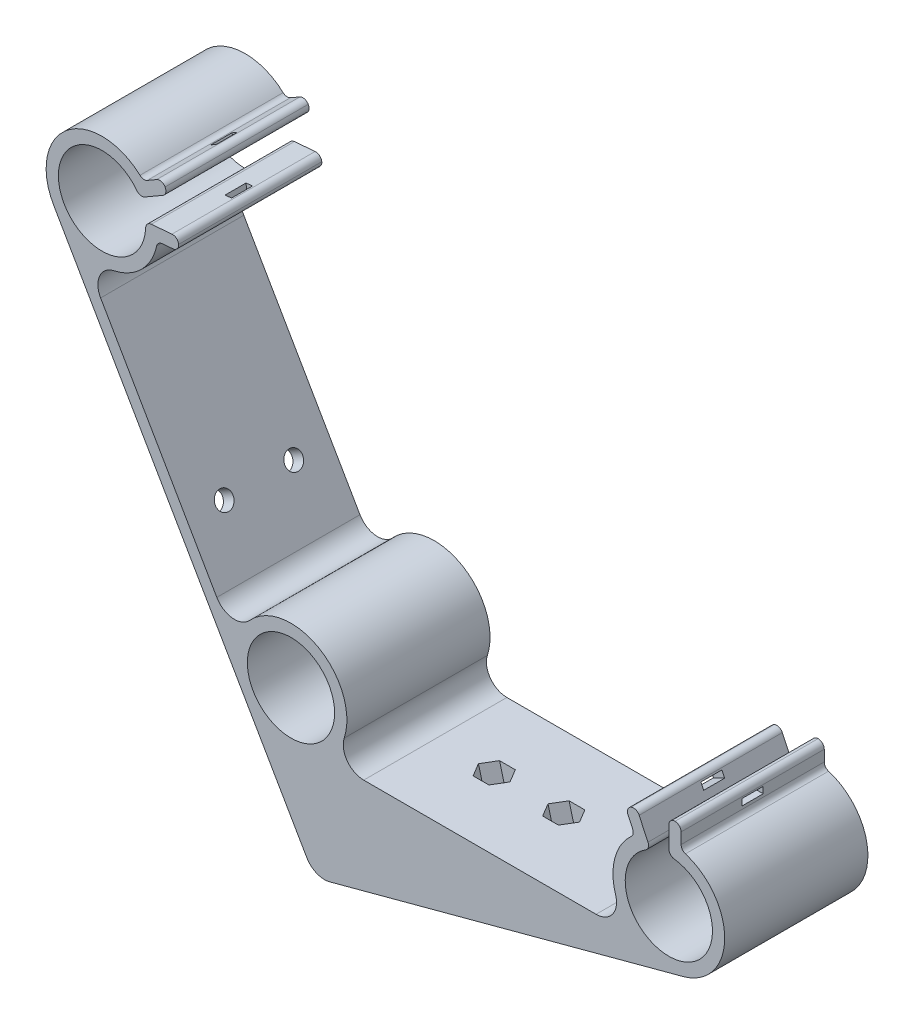
SolidWorks part; units mm, degrees
ref_plane "Front Plane" through (0, 0, 0) normal (0, 0, 1) x (1, 0, 0)
ref_plane "Top Plane" through (0, 0, 0) normal (0, 1, 0) x (1, 0, 0)
ref_plane "Right Plane" through (0, 0, 0) normal (1, 0, 0) x (0, 0, -1)
sketch "Sketch3" plane through (0, 0, 0) normal (0, 1, 0) x (1, 0, 0)
  line L1 (-57.15, -9.525) -> (57.15, -9.525)
  line L2 (-57.15, -9.525) -> (-57.15, 9.525)
  line L3 (-57.15, 9.525) -> (57.15, 9.525)
  line L4 (57.15, -9.525) -> (57.15, 9.525)
  line L5 (-57.15, -9.525) -> (57.15, 9.525) construction
  line L6 (-57.15, 9.525) -> (57.15, -9.525) construction
  point P0 (0, 0)
  dimension "D1" = 19.05
  dimension "D2" = 114.3
extrude "Boss-Extrude1" add sketch "Sketch3" along normal blind 3.81
sketch "Sketch4" plane through (0, 0, 0) normal (0, 0, 1) x (1, 0, 0)
  line L0 (-58.6588, 17.3553) -> (58.6588, 17.3553) construction
  line L1 (57.15, 3.81) -> (-57.15, 3.81) construction
  line L2 (0, -20.955) -> (0, 20.955) construction
  line L5 (-117.3176, 118.9553) -> (-102.2874, 127.633) construction
  line L8 (-57.15, 3.81) -> (57.15, 3.81) construction
  line L9 (-36.0719, 3.81) -> (36.0719, 3.81)
  line L11 (-57.15, 0) -> (57.15, 0) construction
  line L13 (0, 3.81) -> (0, 0)
  line L14 (58.6588, 0) -> (-58.6588, 0)
  line L15 (-58.6588, 17.3553) -> (-24.1786, 77.0768) construction
  line L16 (58.6588, 17.3553) -> (41.5671, 14.3416) construction
  line L17 (58.6588, 17.3553) -> (58.6588, 34.7106) construction
  line L18 (58.6588, 17.3553) -> (64.5947, 33.664) construction
  line L19 (41.5671, 14.3416) -> (45.3193, 15.0032)
  line L20 (58.6588, 34.7106) -> (58.6588, 30.9006)
  line L21 (-132.3477, 110.2777) -> (-73.6889, 8.6777)
  line L22 (-81.6828, 30.1435) -> (-117.7547, 92.6218)
  line L24 (-102.2874, 127.633) -> (-105.587, 125.728)
  line L25 (63.1507, 0.5914) -> (-46.6063, -28.8179)
  line L26 (-117.3176, 118.9553) -> (-100.0283, 120.4679) construction
  line L27 (-73.6889, 8.6777) -> (-53.749, -25.8593)
  line L28 (-73.6889, 8.6777) -> (-46.8802, -37.7565) construction
  line L29 (-100.0283, 120.4679) -> (-103.8238, 120.1359)
  line L30 (-102.2874, 127.633) -> (-96.7882, 130.808)
  line L31 (-96.7882, 130.808) -> (-98.6932, 134.1075)
  line L32 (-98.6932, 134.1075) -> (-104.5591, 130.7208)
  line L33 (-100.0283, 120.4679) -> (-93.7025, 121.0214)
  line L34 (-93.7025, 121.0214) -> (-93.3704, 117.2259)
  line L35 (-93.3704, 117.2259) -> (-100.118, 116.6355)
  line L36 (58.6588, 34.7106) -> (58.6588, 30.9006)
  line L37 (51.3241, 33.0846) -> (52.9343, 29.6315)
  line L38 (45.1875, 37.2294) -> (48.05, 31.0907)
  line L39 (48.6405, 38.8396) -> (45.1875, 37.2294)
  line L40 (51.3241, 33.0846) -> (48.6405, 38.8396)
  line L41 (58.6588, 34.7106) -> (58.6588, 41.0606)
  line L42 (58.6588, 41.0606) -> (62.4688, 41.0606)
  line L43 (62.4688, 41.0606) -> (62.4688, 34.2873)
  circle A0 centre (-58.6588, 17.3553) radius 13.5453
  arc A1 (45.3193, 15.0032) -> (63.2916, 30.0837) centre (58.6588, 17.3553) ccw
  arc A2 (-42.1223, 12.0874) -> (-76.0141, 17.3553) centre (-58.6588, 17.3553) ccw
  arc A3 (42.1223, 12.0874) -> (41.5671, 14.3416) centre (58.6588, 17.3553) cw
  arc A4 (-36.0719, 3.81) -> (-42.1223, 12.0874) centre (-36.0719, 10.16) cw
  arc A5 (36.0719, 3.81) -> (42.1223, 12.0874) centre (36.0719, 10.16) ccw
  arc A6 (42.1223, 12.0874) -> (41.5671, 14.3416) centre (58.6588, 17.3553) cw
  arc A7 (-42.1223, 12.0874) -> (-76.0141, 17.3553) centre (-58.6588, 17.3553) ccw
  arc A8 (41.5671, 14.3416) -> (42.1223, 12.0874) centre (58.6588, 17.3553) ccw
  arc A9 (64.5947, 33.664) -> (76.0141, 17.3553) centre (58.6588, 17.3553) cw
  arc A10 (64.5947, 33.664) -> (76.0141, 17.3553) centre (58.6588, 17.3553) cw
  arc A11 (58.6588, 0) -> (64.5947, 33.664) centre (58.6588, 17.3553) ccw
  arc A12 (63.2916, 30.0837) -> (58.6588, 30.9006) centre (58.6588, 17.3553) ccw
  arc A13 (64.5947, 33.664) -> (58.6588, 34.7106) centre (58.6588, 17.3553) ccw
  arc A15 (-76.0141, 17.3553) -> (-58.6588, 0) centre (-58.6588, 17.3553) ccw
  arc A16 (-132.3477, 110.2777) -> (-106.1618, 132.2503) centre (-117.3176, 118.9553) cw
  arc A17 (-113.6114, 102.0003) -> (-111.3817, 102.6467) centre (-117.3176, 118.9553) ccw
  arc A18 (-106.1618, 132.2503) -> (-102.2874, 127.633) centre (-117.3176, 118.9553) cw
  arc A19 (-108.6108, 129.3316) -> (-105.587, 125.728) centre (-117.3176, 118.9553) cw
  arc A20 (-106.1618, 132.2503) -> (-125.9952, 133.9855) centre (-117.3176, 118.9553) ccw
  arc A21 (-112.6848, 106.2269) -> (-108.6108, 129.3316) centre (-117.3176, 118.9553) cw
  arc A22 (-117.7547, 92.6218) -> (-113.6114, 102.0003) centre (-112.2554, 95.7968) cw
  arc A23 (-49.9811, 2.3252) -> (-73.6889, 8.6777) centre (-58.6588, 17.3553) cw
  arc A24 (-81.6828, 30.1435) -> (-71.4892, 29.0424) centre (-76.1836, 33.3185) ccw
  arc A25 (-71.4892, 29.0424) -> (-49.9811, 2.3252) centre (-58.6588, 17.3553) cw
  arc A26 (-46.6063, -28.8179) -> (-53.749, -25.8593) centre (-48.2498, -22.6843) cw
  arc A27 (-105.587, 125.728) -> (-103.8238, 120.1359) centre (-117.3176, 118.9553) ccw
  arc A28 (-102.2874, 127.633) -> (-100.0283, 120.4679) centre (-117.3176, 118.9553) ccw
  arc A29 (58.6588, 30.9006) -> (52.9343, 29.6315) centre (58.6588, 17.3553) cw
  arc A30 (63.2916, 30.0837) -> (58.6588, 30.9006) centre (58.6588, 17.3553) ccw
  arc A31 (58.6588, 34.7106) -> (51.3241, 33.0846) centre (58.6588, 17.3553) cw
  point P6 (0, 17.3553)
  point P28 (-47.8084, 3.81)
  dimension "D1" = 27.0906
  dimension "D4" = 3.81
  dimension "D5" = 6.35
  dimension "D9" = 6.35
  dimension "D2" = 117.3176
  dimension "D3" = 60
  dimension "D6" = 100
  dimension "D7" = 20
  dimension "D8" = 15
  dimension "D10" = 25
  dimension "D11" = 3.81
  dimension "D12" = 6.35
  dimension "D13" = 3.81
  dimension "D14" = 6.35
sketch "Sketch5" plane through (0, 3.81, 0) normal (0, 1, 0) x (1, 0, 0)
  line L0 (0, -14.8995) -> (0, 14.8995) construction
  line L1 (57.15, 9.525) -> (-57.15, 9.525) construction
  line L2 (0, 13.545) -> (0, 9.525) construction
  line L3 (-95.7369, 0) -> (95.7369, 0) construction
  line L4 (0, -13.545) -> (0, -9.525) construction
  line L5 (-17.78, 9.525) -> (-17.78, -9.525) construction
  line L6 (-57.15, -9.525) -> (57.15, -9.525) construction
  circle A0 centre (0, 10.795) radius 2.75 construction
  circle A1 centre (0, -10.795) radius 2.75 construction
  circle A2 centre (-17.78, 10.795) radius 2.75 construction
  circle A3 centre (-17.78, -10.795) radius 2.75 construction
  circle A4 centre (-17.78, 0) radius 2.75
  circle A5 centre (3.81, 0) radius 2.75
  dimension "D2" = 5.5
  dimension "D1" = 21.59
  dimension "D4" = 21.59
  dimension "D3" = 17.78
extrude "Boss-Extrude2" add sketch "Sketch4" along normal mid plane 44.45 contours A0 A2 L13 L9 A4 | A5 L9 L13 A6 A1 A3 | A25 A2 A7 A15 A23 A0 | A24 L22 A22 A17 A21 A19 L24 A18 A16 L21 A15 A7 | A26 L14 A15 L27 | A28 L21 A15 A7 A24 L22 A22 | L32 A18 L30 L31 | A28 L35 L34 L33 | A31 A11 A9 A13 L20 A12 A1 L19 A3 | A31 L19 A29 L37 | L38 A31 L40 L39 | A13 L43 L42 L41 region at (-27.6447, 2.2944, 0) region at (27.6447, 2.2944, 0) region at (-45.5221, 6.78, 0) region at (-19.9969, -9.8836, 0) region at (-101.0313, 60.6249, 0) region at (42.2818, 13.3222, 0) region at (45.8473, 24.0246, 0) region at (48.2673, 35.0835, 0) region at (-133.6074, 123.3201, 0) region at (60.5844, 37.8142, 0) region at (-96.7687, 118.8201, 0) region at (-100.5625, 130.8524, 0)
extrude "Cut-Extrude4" [suppressed] cut sketch "Sketch5" against normal blind 12.7
sketch "Sketch6" plane through (-48.2096, -27.8338, 0) normal (0.866, 0.5, 0) x (0, 0, -1)
  line L0 (-22.225, 103.0183) -> (22.225, 103.0183) construction
  line L1 (-22.225, 66.9465) -> (-22.225, 139.0902) construction
  line L2 (22.225, 66.9465) -> (22.225, 139.0902) construction
  line L3 (-22.225, 85.2383) -> (22.225, 85.2383) construction
  line L4 (0, 95.7369) -> (0, -95.7369) construction
  circle A0 centre (-10.795, 85.2383) radius 2.75
  circle A1 centre (10.795, 85.2383) radius 2.75
  dimension "D1" = 5.5
  dimension "D2" = 21.59
  dimension "D3" = 17.78
extrude "Cut-Extrude5" cut sketch "Sketch6" against normal blind 7.62
sketch "Sketch7" plane through (4.0825, -15.2359, 0) normal (0.2588, -0.9659, 0) x (0.9659, 0.2588, 0)
  ellipse E0 centre (4.6663, 0) end of major axis (4.6663, -2.75) minor radius 2.6563 construction
  ellipse E1 centre (-16.1881, 0) end of major axis (-16.1881, -2.75) minor radius 2.6563 construction
  ellipse E2 centre (4.6663, 0) end of major axis (4.6663, -2.75) minor radius 2.6563
  ellipse E3 centre (-16.1881, 0) end of major axis (-16.1881, -2.75) minor radius 2.6563
extrude "Cut-Extrude7" cut sketch "Sketch7" against normal up to next
sketch "Sketch11" plane through (4.0825, -15.2359, 0) normal (0.2588, -0.9659, 0) x (0.9659, 0.2588, 0)
  line L0 (95.7369, 0) -> (-95.7369, 0) construction
  line L1 (-11.4538, 0) -> (-13.8209, 4.1)
  line L2 (-13.8209, 4.1) -> (-18.5552, 4.1)
  line L3 (-18.5552, 4.1) -> (-20.9223, 0)
  line L4 (-20.9223, 0) -> (-18.5552, -4.1)
  line L5 (-18.5552, -4.1) -> (-13.8209, -4.1)
  line L6 (-13.8209, -4.1) -> (-11.4538, 0)
  line L7 (9.4006, 0) -> (7.0334, 4.1)
  line L8 (7.0334, 4.1) -> (2.2991, 4.1)
  line L9 (2.2991, 4.1) -> (-0.068, 0)
  line L10 (-0.068, 0) -> (2.2991, -4.1)
  line L11 (2.2991, -4.1) -> (7.0334, -4.1)
  line L12 (7.0334, -4.1) -> (9.4006, 0)
  circle A0 centre (-16.1881, 0) radius 4.1 construction
  circle A1 centre (4.6663, 0) radius 4.1 construction
  dimension "D1" = 8.2
  dimension "D2" = 60
  dimension "D3" = 60
extrude "Cut-Extrude8" cut sketch "Sketch11" against normal up to next from offset 12.7 offset against normal yes
sketch "Sketch14" plane through (-82.7436, 143.316, 0) normal (-0.5, 0.866, 0) x (0.866, 0.5, 0)
  line L0 (-25.1904, 0) -> (-18.417, 0) construction
  line L1 (-25.1904, -22.225) -> (-25.1904, 22.225) construction
  line L2 (-18.417, -22.225) -> (-18.417, 22.225) construction
  line L4 (-22.8037, -3.25) -> (-20.8037, -3.25)
  line L5 (-22.8037, -3.25) -> (-22.8037, 3.25)
  line L6 (-22.8037, 3.25) -> (-20.8037, 3.25)
  line L7 (-20.8037, -3.25) -> (-20.8037, 3.25)
  line L8 (-22.8037, -3.25) -> (-20.8037, 3.25) construction
  line L9 (-22.8037, 3.25) -> (-20.8037, -3.25) construction
  point P6 (-21.8037, 0)
  dimension "D1" = 6.5
  dimension "D2" = 2
extrude "Cut-Extrude9" cut sketch "Sketch14" against normal up to next
ref_plane "Plane1" through (-44.7233, 141.8442, 0) normal (0.3007, -0.9537, 0) x (-0.9537, -0.3007, 0)
mirror "Mirror1" about plane through (-44.7233, 141.8442, 0) normal (0.3007, -0.9537, 0) of "Cut-Extrude9"
ref_plane "Plane2" through (-51.5092, 29.7388, 0) normal (0.866, -0.5, 0) x (0.5, 0.866, 0)
mirror "Mirror2" about plane through (-51.5092, 29.7388, 0) normal (0.866, -0.5, 0) of "Mirror1", "Cut-Extrude9"
fillet "Fillet1" radius 1.905 16 edges at (-105.587, 125.728, 0) (-103.8238, 120.1359, 0) (-100.118, 116.6355, 0) (-104.5591, 130.7208, 0) (52.9343, 29.6315, 0) (58.6588, 30.9006, 0) (48.05, 31.0907, 0) (62.4688, 34.2873, 0) (62.4688, 41.0606, 0) (45.1875, 37.2294, 0) (48.6405, 38.8396, 0) (58.6588, 41.0606, 0) (-93.3704, 117.2259, 0) (-93.7025, 121.0214, 0) (-96.7882, 130.808, 0) (-98.6932, 134.1075, 0)
sketch "Sketch15" [suppressed] plane through (0, 0, 9.525) normal (0, 0, 1) x (1, 0, 0)
  line L4 (-104.0393, 126.6215) -> (-98.438, 129.8555)
  line L8 (-100.343, 133.155) -> (-103.2939, 131.4513)
  line L11 (-132.3477, 110.2777) -> (-53.749, -25.8593)
  line L20 (36.0719, 3.81) -> (-36.0719, 3.81)
  line L23 (-132.3477, 110.2777) -> (-53.749, -25.8593)
  line L32 (36.0719, 3.81) -> (-36.0719, 3.81)
  line L36 (-46.6063, -28.8179) -> (63.1507, 0.5914)
  line L37 (-46.6063, -28.8179) -> (63.1507, 0.5914)
  line L38 (62.4688, 35.7482) -> (62.4688, 39.1556)
  line L39 (62.4688, 35.7482) -> (62.4688, 39.1556)
  line L40 (58.6588, 39.1556) -> (58.6588, 32.6877)
  line L41 (58.6588, 39.1556) -> (58.6588, 32.6877)
  line L42 (52.179, 31.2512) -> (49.4456, 37.1131)
  line L43 (52.179, 31.2512) -> (49.4456, 37.1131)
  line L44 (45.9925, 35.5029) -> (47.4326, 32.4148)
  line L45 (45.9925, 35.5029) -> (47.4326, 32.4148)
  line L46 (-81.6828, 30.1435) -> (-117.7547, 92.6218)
  line L47 (-98.6626, 116.7629) -> (-95.2682, 117.0598)
  line L48 (-95.6002, 120.8553) -> (-102.0435, 120.2916)
  arc A0 (-49.9811, 2.3252) -> (-71.4892, 29.0424) centre (-58.6588, 17.3553) ccw construction
  arc A1 (-73.6889, 8.6777) -> (-49.9811, 2.3252) centre (-58.6588, 17.3553) ccw construction
  arc A2 (-76.0141, 17.3553) -> (-58.6588, 0) centre (-58.6588, 17.3553) ccw construction
  arc A3 (-49.9811, 2.3252) -> (-42.1223, 12.0874) centre (-58.6588, 17.3553) ccw
  arc A4 (-73.6889, 8.6777) -> (-49.9811, 2.3252) centre (-58.6588, 17.3553) ccw
  arc A5 (-73.6889, 8.6777) -> (-58.6588, 0) centre (-58.6588, 17.3553) ccw
  arc A39 (-106.5116, 127.1227) -> (-103.7812, 118.4631) centre (-117.3176, 118.9553) ccw
  arc A40 (-106.5116, 127.1227) -> (-104.0393, 126.6215) centre (-104.9918, 128.2713) ccw
  arc A41 (-98.438, 129.8555) -> (-97.7407, 132.4577) centre (-99.3905, 131.5052) ccw
  arc A42 (-97.7407, 132.4577) -> (-100.343, 133.155) centre (-99.3905, 131.5052) ccw
  arc A43 (-105.5392, 131.702) -> (-103.2939, 131.4513) centre (-104.2464, 133.1011) ccw
  arc A44 (-105.5392, 131.702) -> (-132.3477, 110.2777) centre (-117.3176, 118.9553) ccw
  arc A45 (-53.749, -25.8593) -> (-46.6063, -28.8179) centre (-48.2498, -22.6843) ccw
  arc A46 (-53.749, -25.8593) -> (-46.6063, -28.8179) centre (-48.2498, -22.6843) ccw
  arc A47 (63.1507, 0.5914) -> (63.8085, 33.929) centre (58.6588, 17.3553) ccw
  arc A48 (63.1507, 0.5914) -> (63.8085, 33.929) centre (58.6588, 17.3553) ccw
  arc A51 (62.4688, 35.7482) -> (63.8085, 33.929) centre (64.3738, 35.7482) ccw
  arc A84 (62.4688, 35.7482) -> (63.8085, 33.929) centre (64.3738, 35.7482) ccw
  arc A85 (62.4688, 39.1556) -> (60.5638, 41.0606) centre (60.5638, 39.1556) ccw
  arc A86 (62.4688, 39.1556) -> (60.5638, 41.0606) centre (60.5638, 39.1556) ccw
  arc A87 (60.5638, 41.0606) -> (58.6588, 39.1556) centre (60.5638, 39.1556) ccw
  arc A88 (60.5638, 41.0606) -> (58.6588, 39.1556) centre (60.5638, 39.1556) ccw
  arc A89 (58.6588, 32.6877) -> (60.3289, 30.7973) centre (60.5638, 32.6877) ccw
  arc A90 (58.6588, 32.6877) -> (60.3289, 30.7973) centre (60.5638, 32.6877) ccw
  arc A91 (51.4643, 28.832) -> (60.3289, 30.7973) centre (58.6588, 17.3553) ccw
  arc A92 (51.4643, 28.832) -> (60.3289, 30.7973) centre (58.6588, 17.3553) ccw
  arc A93 (51.4643, 28.832) -> (52.179, 31.2512) centre (50.4525, 30.4461) ccw
  arc A94 (51.4643, 28.832) -> (52.179, 31.2512) centre (50.4525, 30.4461) ccw
  arc A95 (49.4456, 37.1131) -> (46.914, 38.0345) centre (47.7191, 36.308) ccw
  arc A96 (49.4456, 37.1131) -> (46.914, 38.0345) centre (47.7191, 36.308) ccw
  arc A97 (46.914, 38.0345) -> (45.9925, 35.5029) centre (47.7191, 36.308) ccw
  arc A98 (46.914, 38.0345) -> (45.9925, 35.5029) centre (47.7191, 36.308) ccw
  arc A99 (46.9872, 30.1998) -> (47.4326, 32.4148) centre (45.7061, 31.6097) ccw
  arc A100 (46.9872, 30.1998) -> (47.4326, 32.4148) centre (45.7061, 31.6097) ccw
  arc A101 (46.9872, 30.1998) -> (42.1223, 12.0874) centre (58.6588, 17.3553) ccw
  arc A102 (46.9872, 30.1998) -> (42.1223, 12.0874) centre (58.6588, 17.3553) ccw
  arc A103 (36.0719, 3.81) -> (42.1223, 12.0874) centre (36.0719, 10.16) ccw
  arc A104 (36.0719, 3.81) -> (42.1223, 12.0874) centre (36.0719, 10.16) ccw
  arc A105 (-42.1223, 12.0874) -> (-36.0719, 3.81) centre (-36.0719, 10.16) ccw
  arc A106 (-42.1223, 12.0874) -> (-36.0719, 3.81) centre (-36.0719, 10.16) ccw
  arc A107 (-42.1223, 12.0874) -> (-71.4892, 29.0424) centre (-58.6588, 17.3553) ccw
  arc A108 (-81.6828, 30.1435) -> (-71.4892, 29.0424) centre (-76.1836, 33.3185) ccw
  arc A109 (-113.6114, 102.0003) -> (-117.7547, 92.6218) centre (-112.2554, 95.7968) ccw
  arc A110 (-113.6114, 102.0003) -> (-100.3581, 115.2697) centre (-117.3176, 118.9553) ccw
  arc A111 (-98.6626, 116.7629) -> (-100.3581, 115.2697) centre (-98.4966, 114.8651) ccw
  arc A112 (-95.2682, 117.0598) -> (-93.5364, 119.1236) centre (-95.4342, 118.9576) ccw
  arc A113 (-93.5364, 119.1236) -> (-95.6002, 120.8553) centre (-95.4342, 118.9576) ccw
  arc A114 (-102.0435, 120.2916) -> (-103.7812, 118.4631) centre (-101.8775, 118.3939) ccw
  dimension "D1" = 0
extrude "Cut-Extrude10" [suppressed] cut sketch "Sketch15" against normal through all both and the other way through all
sketch "Sketch16" [suppressed] plane through (-48.2096, -27.8338, 0) normal (0.866, 0.5, 0) x (0, 0, -1)
  line L0 (-9.525, 103.0183) -> (9.525, 103.0183) construction
  line L1 (-9.525, 66.9465) -> (-9.525, 139.0902) construction
  line L2 (9.525, 66.9465) -> (9.525, 139.0902) construction
  line L3 (0, 66.9465) -> (0, 139.0902) construction
  circle A0 centre (0, 125.2433) radius 2.75
  circle A1 centre (0, 80.7933) radius 2.75
  dimension "D1" = 5.5
  dimension "D2" = 44.45
extrude "Cut-Extrude11" [suppressed] cut sketch "Sketch16" against normal up to next
